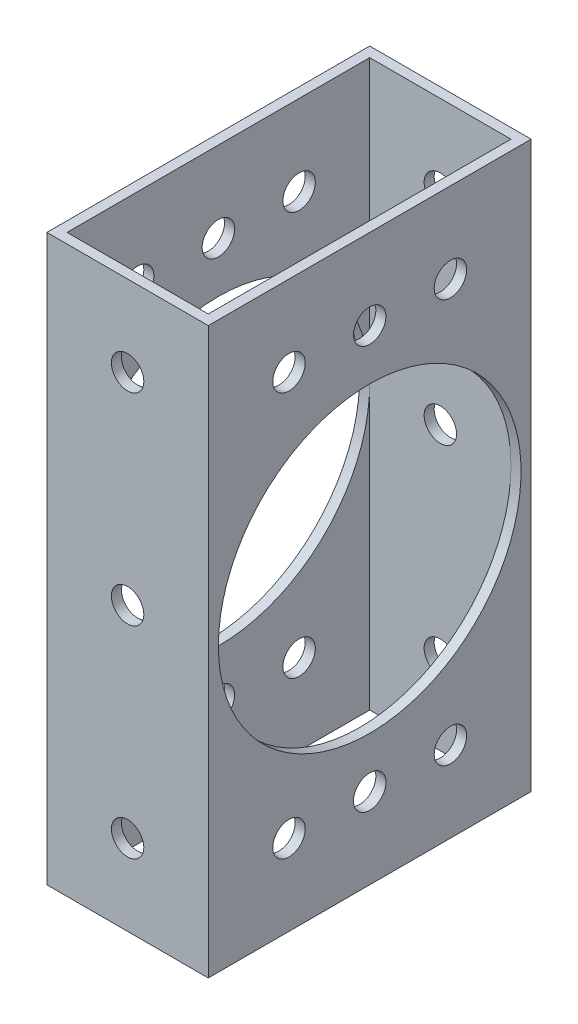
SolidWorks part; units mm, degrees
material "6061-T6 (SS)"
ref_plane "Front" through (0, 0, 0) normal (0, 0, 1) x (1, 0, 0)
ref_plane "Top" through (0, 0, 0) normal (0, 1, 0) x (1, 0, 0)
ref_plane "Right" through (0, 0, 0) normal (1, 0, 0) x (0, 0, -1)
sketch "Sketch1" plane through (0, 0, 0) normal (0, 1, 0) x (1, 0, 0)
  line L1 (12.7, 25.4) -> (-12.7, 25.4)
  line L2 (12.7, 25.4) -> (12.7, -25.4)
  line L3 (12.7, -25.4) -> (-12.7, -25.4)
  line L4 (-12.7, 25.4) -> (-12.7, -25.4)
  line L5 (12.7, 25.4) -> (-12.7, -25.4) construction
  line L6 (12.7, -25.4) -> (-12.7, 25.4) construction
  point P0 (0, 0)
  dimension "D1" = 25.4
  dimension "D2" = 50.8
extrude "Extrude-Thin1" add sketch "Sketch1" along normal up to surface (88.9 mm away) thin thin type one direction reverse wall 1.5875
sketch "Sketch4" plane through (-12.7, 0, 0) normal (-1, 0, 0) x (0, 0, 1)
  line L0 (-12.7, 12.7) -> (12.7, 12.7) construction
  line L3 (-12.7, 76.2) -> (12.7, 76.2) construction
  line L5 (-25.4, 0) -> (25.4, 0) construction
  line L6 (-25.4, 88.9) -> (25.4, 88.9) construction
  point P0 (-12.7, 76.2)
  point P2 (0, 76.2)
  point P4 (12.7, 76.2)
  point P6 (-12.7, 12.7)
  point P8 (0, 12.7)
  point P10 (12.7, 12.7)
  dimension "D1" = 12.7
  dimension "D2" = 12.7
  dimension "D3" = 12.7
  dimension "D4" = 12.7
hole_wizard "#10 Clearance Hole1" positions "Sketch4" profile "Sketch3" hole size "#10" standard "ANSI Inch" end condition through all
sketch "Sketch3" plane through (-12.7, 76.2, -12.7) normal (0, 1, 0) x (0, 0, 1)
  line L0 (0, 0) -> (0, 25.4)
  line L1 (0, 25.4) -> (2.5527, 25.4)
  line L2 (2.5527, 25.4) -> (2.5527, 0)
  line L5 (2.5527, 0) -> (0, 0)
  line L11 (0, -6.35) -> (0, 107.95) construction
  dimension "Thru Hole Dia." = 5.1054
  dimension "Thru Hole Depth" = 25.4
sketch "Sketch7" plane through (0, 0, 25.4) normal (0, 0, 1) x (1, 0, 0)
  line L0 (-12.7, 0) -> (12.7, 0) construction
  line L1 (-12.7, 88.9) -> (12.7, 88.9) construction
  line L2 (0, 12.7) -> (0, 76.2) construction
  point P0 (0, 12.7)
  point P2 (0, 76.2)
  point P10 (0, 44.45)
  dimension "D1" = 12.7
  dimension "D2" = 12.7
hole_wizard "#10 Clearance Hole2" positions "Sketch7" profile "Sketch6" hole size "#10" standard "ANSI Inch" end condition through all
sketch "Sketch6" plane through (0, 12.7, 25.4) normal (1, 0, 0) x (0, -1, 0)
  line L0 (0, 0) -> (0, 50.8)
  line L1 (0, 50.8) -> (2.5527, 50.8)
  line L2 (2.5527, 50.8) -> (2.5527, 0)
  line L5 (2.5527, 0) -> (0, 0)
  line L11 (0, -6.35) -> (0, 107.95) construction
  dimension "Thru Hole Dia." = 5.1054
  dimension "Thru Hole Depth" = 50.8
sketch "Sketch8" plane through (-12.7, 0, 0) normal (-1, 0, 0) x (0, 0, 1)
  line L0 (-25.4, 0) -> (25.4, 88.9) construction
  line L1 (25.4, 88.9) -> (25.4, 0) construction
  line L2 (-25.4, 88.9) -> (25.4, 88.9) construction
  line L3 (-25.4, 88.9) -> (-25.4, 0) construction
  line L4 (-25.4, 0) -> (25.4, 0) construction
  circle A0 centre (0, 44.45) radius 23.8125
  dimension "D1" = 47.625
extrude "Cut-Extrude1" cut sketch "Sketch8" against normal through all
